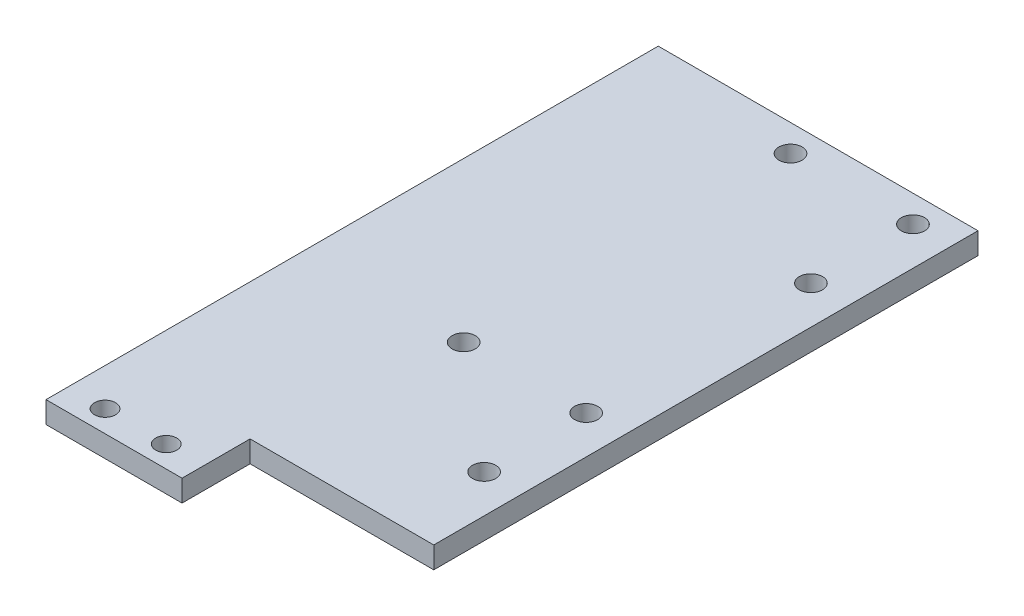
SolidWorks part; units mm, degrees
material "6061 Alloy"
ref_plane "Front Plane" through (0, 0, 0) normal (0, 0, 1) x (1, 0, 0)
ref_plane "Top Plane" through (0, 0, 0) normal (0, 1, 0) x (1, 0, 0)
ref_plane "Right Plane" through (0, 0, 0) normal (1, 0, 0) x (0, 0, -1)
sketch "Sketch1" plane through (0, 0, 0) normal (0, 1, 0) x (1, 0, 0)
  line L0 (0, 0) -> (0, 90)
  line L1 (0, 90) -> (47, 90)
  line L2 (47, 90) -> (47, 10)
  line L3 (47, 10) -> (20, 10)
  line L4 (20, 10) -> (20, 0)
  line L5 (0, 0) -> (20, 0)
  line L16 (20, 0) -> (20, 6.35) construction
  line L17 (14.5, 3.175) -> (5.5, 3.175) construction
  circle A5 centre (41.4, 86.0411) radius 1.7
  circle A6 centre (14.5, 3.175) radius 1.55
  circle A7 centre (23.4, 86.0411) radius 1.7
  circle A9 centre (5.5, 3.175) radius 1.55
  circle A12 centre (41.4, 23) radius 1.7 construction
  circle A13 centre (41.4, 38) radius 1.7 construction
  circle A14 centre (23.4, 38) radius 1.7 construction
  circle A15 centre (41.4, 23) radius 1.7
  circle A16 centre (41.4, 38) radius 1.7
  circle A17 centre (23.4, 38) radius 1.7
  circle A18 centre (41.4, 71.0411) radius 1.7
  point P20 (10, 3.175)
  point P21 (10, 0)
  point P26 (0, 0)
  dimension "D2" = 3.1
  dimension "D3" = 3.1
  dimension "D1" = 80
  dimension "D9" = 47
  dimension "D11" = 10
  dimension "D4" = 9
  dimension "D5" = 3.175
  dimension "D6" = 15
extrude "Boss-Extrude1" add sketch "Sketch1" along normal blind 3.175
equation "\"D3@Sketch1\"=\"D2@Sketch1\""
